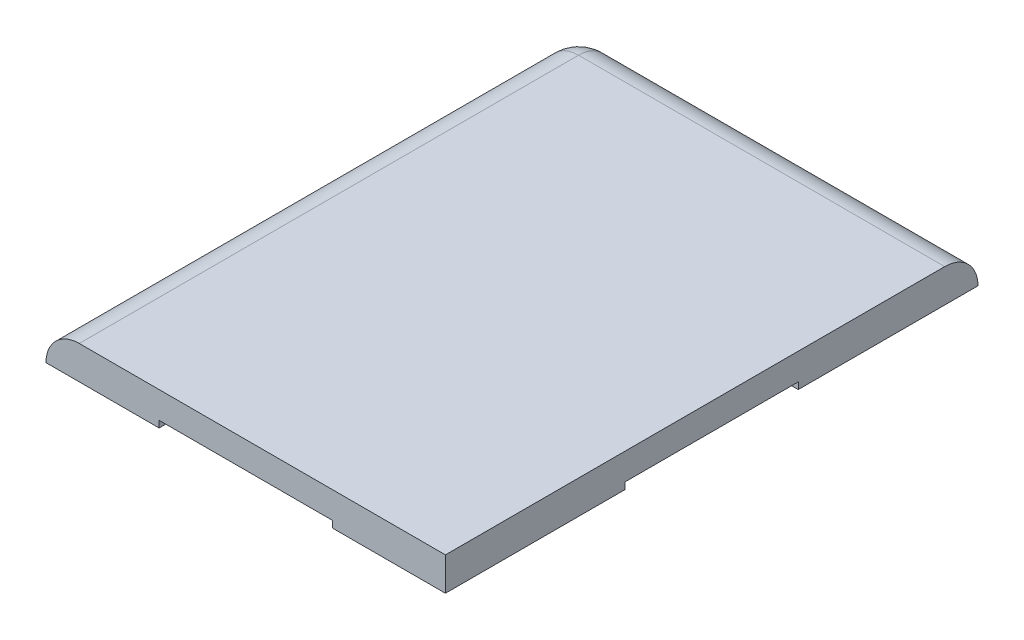
SolidWorks part; units mm, degrees
ref_plane "Plan de face" through (0, 0, 0) normal (0, 0, 1) x (1, 0, 0)
ref_plane "Plan de dessus" through (0, 0, 0) normal (0, 1, 0) x (1, 0, 0)
ref_plane "Plan de droite" through (0, 0, 0) normal (1, 0, 0) x (0, 0, -1)
sketch "Esquisse1" plane through (0, 0, 0) normal (0, 1, 0) x (1, 0, 0)
  line L1 (0, 0) -> (120, 0)
  line L2 (0, 0) -> (0, 160)
  line L3 (0, 160) -> (120, 160)
  line L4 (120, 0) -> (120, 160)
  dimension "D1" = 120
  dimension "D2" = 160
extrude "Boss.-Extru.1" add sketch "Esquisse1" along normal blind 10
fillet "Congé1" radius 10 1 edges at (0, 10, -80)
fillet "Congé2" radius 10 2 edges at (2.9289, 7.0711, -160) (65, 10, -160)
sketch "Esquisse2" plane through (0, 0, 0) normal (0, -1, 0) x (1, 0, 0)
  line L0 (0, -150) -> (0, 0) construction
  line L1 (120, -160) -> (10, -160) construction
  circle A0 centre (8, -152) radius 2.5
  dimension "D3" = 5
  dimension "D1" = 8
  dimension "D2" = 8
extrude "Boss.-Extru.2" add sketch "Esquisse2" along normal blind 30
sketch "Esquisse3" plane through (0, 0, 0) normal (0, -1, 0) x (1, 0, 0)
  line L0 (120, 0) -> (120, -160) construction
  line L1 (120, -106) -> (109, -106)
  line L2 (120, -106) -> (120, -54)
  line L3 (120, -54) -> (109, -54)
  line L4 (109, -106) -> (109, -54)
  line L5 (0, 0) -> (120, 0) construction
  line L6 (34, 0) -> (86, 0)
  line L7 (34, 0) -> (34, -11)
  line L8 (34, -11) -> (86, -11)
  line L9 (86, 0) -> (86, -11)
  line L10 (120, -160) -> (10, -160) construction
  line L11 (0, -150) -> (0, 0) construction
  point P14 (114.5, -106)
  dimension "D1" = 54
  dimension "D2" = 54
  dimension "D3" = 11
  dimension "D4" = 34
  dimension "D5" = 34
  dimension "D6" = 11
extrude "Enlèv. mat.-Extru.1" cut sketch "Esquisse3" against normal blind 2
